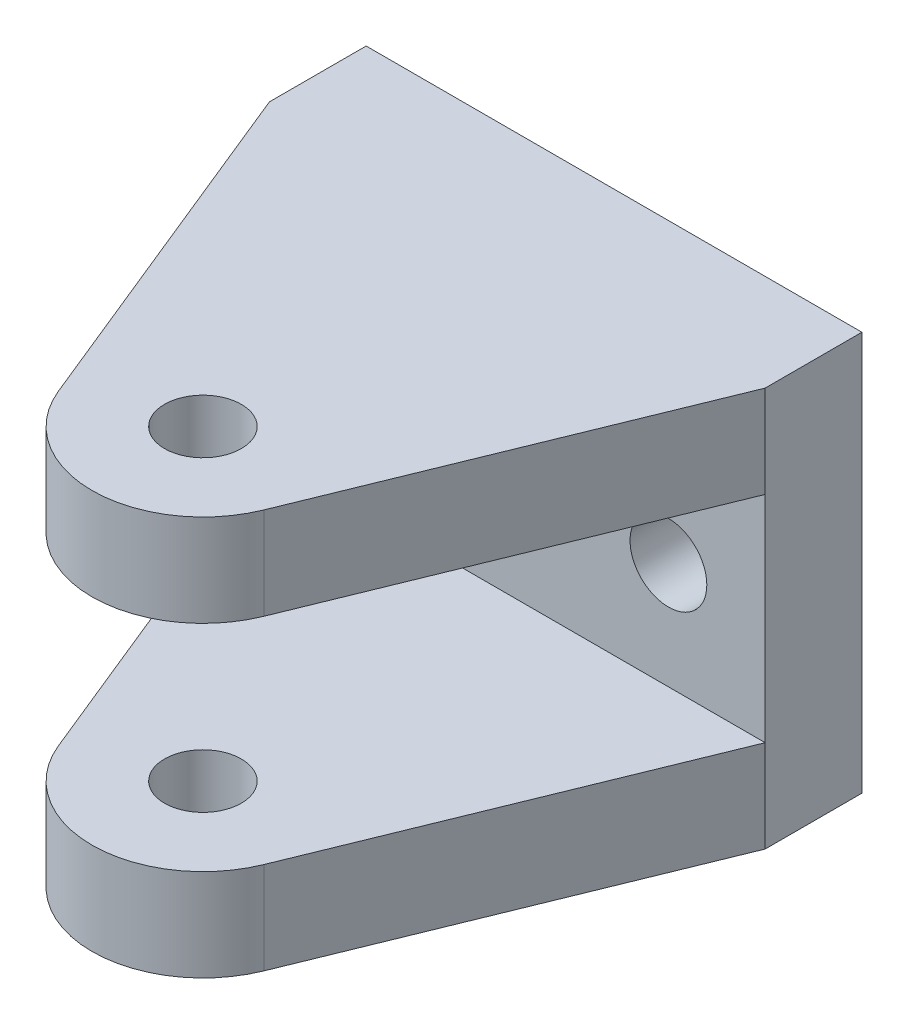
SolidWorks part; units mm, degrees
ref_plane "Front Plane" through (0, 0, 0) normal (0, 0, 1) x (1, 0, 0)
ref_plane "Top Plane" through (0, 0, 0) normal (0, 1, 0) x (1, 0, 0)
ref_plane "Right Plane" through (0, 0, 0) normal (1, 0, 0) x (0, 0, -1)
sketch "Sketch1" plane through (0, 0, 0) normal (0, 0, 1) x (1, 0, 0)
  line L0 (12.5, 0) -> (-12.5, 0) construction
  line L1 (-20.5, -16.51) -> (20.5, -16.51)
  line L2 (-20.5, -16.51) -> (-20.5, 16.51)
  line L3 (-20.5, 16.51) -> (20.5, 16.51)
  line L4 (20.5, -16.51) -> (20.5, 16.51)
  line L5 (-20.5, -16.51) -> (20.5, 16.51) construction
  line L6 (-20.5, 16.51) -> (20.5, -16.51) construction
  circle A0 centre (12.5, 0) radius 3.175
  circle A1 centre (-12.5, 0) radius 3.175
  point P0 (0, 0)
  dimension "D1" = 6.35
  dimension "D2" = 25
  dimension "D3" = 8
  dimension "D4" = 16.51
extrude "Boss-Extrude1" add sketch "Sketch1" along normal blind 8
sketch "Sketch2" plane through (0, 0, 8) normal (0, 0, 1) x (1, 0, 0)
  line L0 (-12.5, 0) -> (12.5, 0) construction
  line L2 (-20.5, 8.89) -> (20.5, 8.89)
  line L3 (-20.5, 8.89) -> (-20.5, 16.51)
  line L4 (-20.5, 16.51) -> (20.5, 16.51)
  line L5 (20.5, 8.89) -> (20.5, 16.51)
  line L6 (-20.5, 8.89) -> (20.5, 16.51) construction
  line L7 (-20.5, 16.51) -> (20.5, 8.89) construction
  line L8 (-20.5, 16.51) -> (-20.5, -16.51) construction
  line L9 (20.5, -8.89) -> (20.5, -16.51)
  line L10 (-20.5, -8.89) -> (-20.5, -16.51)
  line L11 (-20.5, -16.51) -> (20.5, -8.89) construction
  line L12 (-20.5, -8.89) -> (20.5, -16.51) construction
  line L13 (-20.5, -8.89) -> (20.5, -8.89)
  line L14 (-20.5, -16.51) -> (20.5, -16.51)
  circle A0 centre (-12.5, 0) radius 3.175 construction
  circle A1 centre (12.5, 0) radius 3.175 construction
  point P6 (0, 12.7)
  point P21 (0, -12.7)
  dimension "D1" = 17.78
extrude "Boss-Extrude2" add sketch "Sketch2" along normal blind 53
sketch "Sketch3" plane through (0, 0, 0) normal (0, 1, 0) x (1, 0, 0)
  point P0 (0, -34)
  dimension "D1" = 34
ref_point "UBJ Point"
sketch "Sketch4" plane through (0, 0, 0) normal (0, 1, 0) x (1, 0, 0)
  circle A0 centre (0, -34) radius 3.175
  dimension "D1" = 6.35
extrude "Cut-Extrude1" cut sketch "Sketch4" against normal up to surface and the other way up to surface up to face at (0, -16.51, 30.5) other way up to face at (0, 16.51, 30.5)
sketch "Sketch5" plane through (0, 0, 0) normal (0, 1, 0) x (1, 0, 0)
  line L0 (20.5, -8) -> (8.4969, -37.4617)
  line L1 (-8.4969, -37.4617) -> (-20.5, -8)
  line L4 (20.5, 0) -> (-20.5, 0)
  line L5 (-20.5, 0) -> (-20.5, -61)
  line L6 (-20.5, -61) -> (20.5, -61)
  line L7 (20.5, -61) -> (20.5, 0)
  line L9 (-20.5, -8) -> (-20.5, -61)
  line L10 (-20.5, -61) -> (20.5, -61)
  line L11 (20.5, -61) -> (20.5, -8)
  line L12 (20.5, -8) -> (-20.5, -8)
  line L13 (20.5, -61) -> (20.5, -8)
  line L14 (-20.5, -61) -> (20.5, -61)
  line L15 (-20.5, -8) -> (-20.5, -61)
  line L17 (20.5, -61) -> (20.5, -8)
  line L18 (-20.5, -61) -> (20.5, -61)
  line L19 (-20.5, -8) -> (-20.5, -61)
  arc A0 (-8.4969, -37.4617) -> (8.4969, -37.4617) centre (0, -34) ccw
  circle A1 centre (0, -34) radius 3.175 construction
  circle A2 centre (0, -34) radius 3.175 construction
  dimension "D3" = 6
  dimension "D1" = 0
  dimension "D2" = 0
extrude "Cut-Extrude2" cut sketch "Sketch5" against normal up to surface and the other way up to surface contours A0 L1 L9 L10 L11 L0 region at (0, 0, 43.6449) up to face at (0, -16.51, 37.175) other way up to face at (0, 16.51, 30.825)
